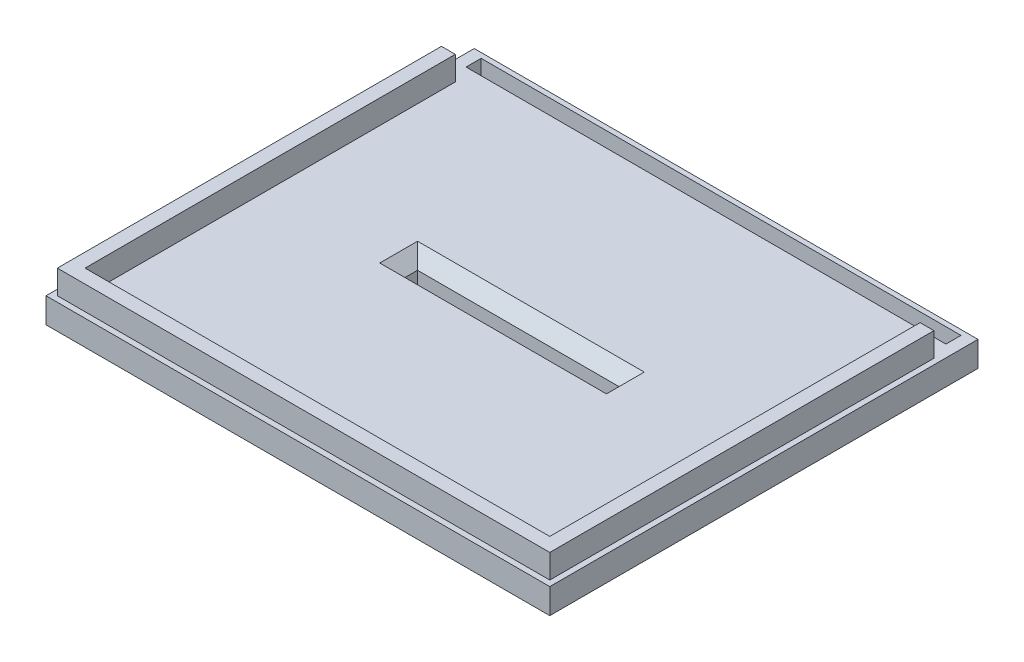
SolidWorks part; units mm, degrees
note: The reader was unsure of these and kept them because the rebuilt part matched: shared geometry of "Croquis1<4>".
ref_plane "Front Plane" through (0, 0, 0) normal (0, 0, 1) x (1, 0, 0)
ref_plane "Top Plane" through (0, 0, 0) normal (0, 1, 0) x (1, 0, 0)
ref_plane "Right Plane" through (0, 0, 0) normal (1, 0, 0) x (0, 0, -1)
sketch "Croquis1" plane through (0, 0, 0) normal (0, 1, 0) x (1, 0, 0)
  line L4 (-100, -85) -> (-100, 85)
  line L5 (97.75, 69.75) -> (97.75, -82.75)
  line L6 (97.75, -82.75) -> (-97.75, -82.75)
  line L7 (-97.75, -82.75) -> (-97.75, 69.75)
  line L8 (-97.75, 69.75) -> (-92.25, 69.75)
  line L9 (-92.25, 69.75) -> (-92.25, -77.25)
  line L10 (-92.25, -77.25) -> (92.25, -77.25)
  line L11 (92.25, -77.25) -> (92.25, 69.75)
  line L12 (92.25, 69.75) -> (97.75, 69.75)
  line L68 (-100, -85) -> (100, -85)
  line L70 (-100, 85) -> (100, 85)
  line L71 (100, -85) -> (100, 85)
  line L73 (-100, 85) -> (100, -85) construction
  dimension "D1" = 200
  dimension "D2" = 170
  dimension "D3" = 100
  dimension "D4" = 85
  dimension "D5" = 2.25
  dimension "D6" = 2.25
  dimension "D7" = 2.25
  dimension "D8" = 5.5
  dimension "D9" = 5.5
  dimension "D10" = 5.5
  dimension "D11" = 15.25
  dimension "D12" = 15.25
extrude "Saliente-Extruir1" add sketch "Croquis1" along normal blind 10
extrude "Saliente-Extruir2" add sketch "Croquis1<4>" along normal blind 19.5
sketch "Croquis1<4>" plane through (0, 0, 0) normal (0, 1, 0) x (1, 0, 0) same geometry as "Croquis1"
sketch "Croquis2" plane through (0, 10, 0) normal (0, 1, 0) x (1, 0, 0)
  line L0 (95.25, 77) -> (84.75, 77)
  line L2 (95.25, 77) -> (95.25, 83)
  line L3 (95.25, 83) -> (84.75, 83)
  line L4 (84.75, 77) -> (84.75, 83)
  line L5 (95.25, 77) -> (84.75, 83) construction
  line L6 (95.25, 83) -> (84.75, 77) construction
  line L7 (90, 83) -> (90, 77)
  line L8 (0, -40.7143) -> (0, 173.0111) construction
  line L9 (-95.25, 83) -> (-84.75, 77) construction
  line L10 (-95.25, 77) -> (-84.75, 83) construction
  line L11 (-90, 83) -> (-90, 77)
  line L12 (-84.75, 77) -> (-84.75, 83)
  line L13 (-95.25, 83) -> (-84.75, 83)
  line L14 (-95.25, 77) -> (-95.25, 83)
  line L15 (-95.25, 77) -> (-84.75, 77)
  line L16 (-100, 85) -> (100, 85) construction
  line L17 (-84.75, 83) -> (84.75, 83)
  line L18 (-84.75, 77) -> (84.75, 77)
  point P0 (90, 80)
  point P16 (-90, 80)
  dimension "D1" = 6
  dimension "D2" = 10.5
  dimension "D3" = 2
  dimension "D4" = 90
extrude "Cortar-Extruir1" cut sketch "Croquis2" against normal blind 20 contours L12 L18 L4 L17 | L11 L15 L12 L13 | L14 L15 L11 L13 | L7 L3 L4 L0 | L3 L7 L0 L2
sketch "Croquis3" plane through (0, 0, 0) normal (0, -1, 0) x (1, 0, 0)
  line L0 (-40, -2.5) -> (-40, 2.5)
  line L1 (-40, -2.5) -> (40, -2.5)
  line L2 (-40, 2.5) -> (40, 2.5)
  line L3 (40, -2.5) -> (40, 2.5)
  line L4 (-40, -2.5) -> (40, 2.5) construction
  line L5 (-40, 2.5) -> (40, -2.5) construction
  point P1 (0, 0)
  dimension "D1" = 80
  dimension "D2" = 5
extrude "Cortar-Extruir2" cut sketch "Croquis3" against normal blind 10
chamfer "Chaflán1" distance 5 angle 45 4 edges at (-40, 10, 0) (0, 10, 2.5) (40, 10, 0) (0, 10, -2.5)
sketch "Croquis4" plane through (0, 0, 0) normal (0, -1, 0) x (1, 0, 0)
  line L0 (43, -4.25) -> (-43, -4.25)
  line L1 (43, -4.25) -> (43, 4.25)
  line L2 (-43, -4.25) -> (-43, 4.25)
  line L3 (43, 4.25) -> (-43, 4.25)
  line L4 (43, -4.25) -> (-43, 4.25) construction
  line L5 (-43, -4.25) -> (43, 4.25) construction
  line L6 (40, -2.5) -> (-40, -2.5)
  line L7 (40, -2.5) -> (40, 2.5)
  line L8 (-40, -2.5) -> (-40, 2.5)
  line L9 (40, 2.5) -> (-40, 2.5)
  line L10 (40, -2.5) -> (-40, 2.5) construction
  line L11 (-40, -2.5) -> (40, 2.5) construction
  line L12 (-46, 7.25) -> (-46, -7.25)
  line L13 (-46, 7.25) -> (46, 7.25)
  line L14 (-46, -7.25) -> (46, -7.25)
  line L15 (46, 7.25) -> (46, -7.25)
  line L16 (-46, 7.25) -> (46, -7.25) construction
  line L17 (-46, -7.25) -> (46, 7.25) construction
  point P1 (0, 0)
  point P2 (0, 0)
  point P3 (0, 0)
  dimension "D1" = 3
  dimension "D2" = 1.75
  dimension "D3" = 3
  dimension "D4" = 3
extrude "Saliente-Extruir3" add sketch "Croquis4" along normal blind 6 contours L15 L13 L12 L14 L3 L1 L0 L2
sketch "Croquis5" plane through (0, -6, 0) normal (0, -1, 0) x (1, 0, 0)
  line L0 (-46, -7.25) -> (-46, 7.25)
  line L1 (-46, -7.25) -> (46, -7.25)
  line L2 (-46, 7.25) -> (46, 7.25)
  line L3 (46, -7.25) -> (46, 7.25)
  line L4 (-46, -7.25) -> (46, 7.25) construction
  line L5 (-46, 7.25) -> (46, -7.25) construction
  point P1 (0, 0)
extrude "Saliente-Extruir4" add sketch "Croquis5" along normal blind 2
sketch "Croquis6" plane through (46, 0, 0) normal (1, 0, 0) x (0, 0, -1)
  line L0 (5.25, 0) -> (5.25, -6)
  line L1 (-7.25, 0) -> (7.25, 0) construction
  line L2 (5.25, -6) -> (-5.25, -6)
  line L3 (-5.25, -6) -> (-5.25, 0)
  line L4 (-5.25, 0) -> (0, 0)
  line L5 (0, 0) -> (5.25, 0)
  dimension "D1" = 5.25
  dimension "D2" = 5.25
  dimension "D3" = 6
extrude "Cortar-Extruir3" cut sketch "Croquis6" against normal blind 90
